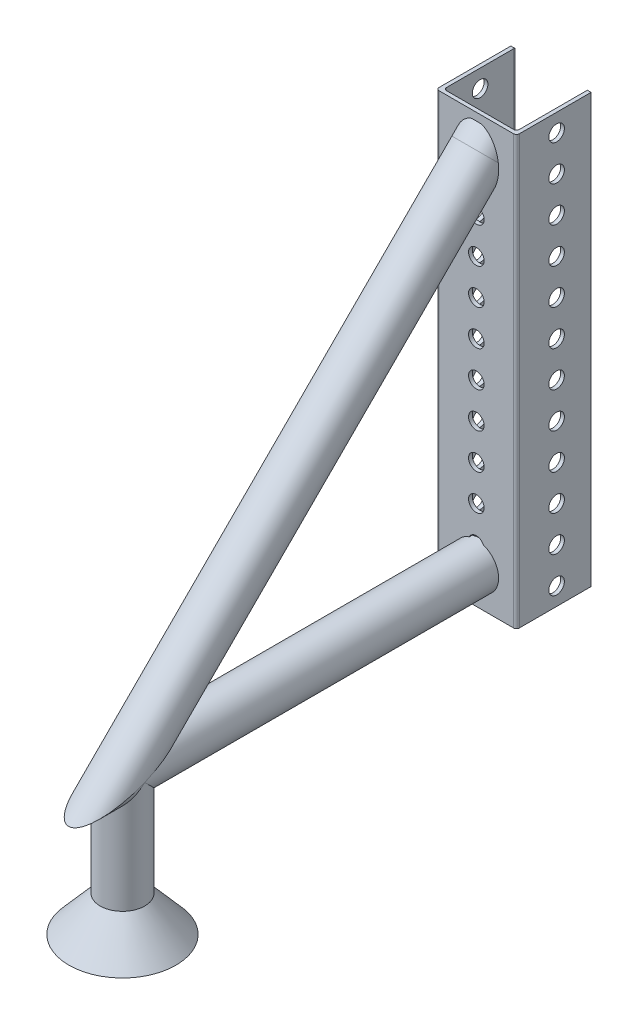
SolidWorks part; units mm, degrees
ref_plane "Front Plane" through (0, 0, 0) normal (0, 0, 1) x (1, 0, 0)
ref_plane "Top Plane" through (0, 0, 0) normal (0, 1, 0) x (1, 0, 0)
ref_plane "Right Plane" through (0, 0, 0) normal (1, 0, 0) x (0, 0, -1)
sketch "Sketch1" plane through (0, 0, 0) normal (0, 1, 0) x (1, 0, 0)
  line L1 (2, 0) -> (55.15, 0)
  line L2 (0, 2) -> (0, 55.15)
  line L3 (2, 57.15) -> (55.15, 57.15)
  line L4 (57.15, 2) -> (57.15, 55.15)
  line L5 (4.667, 54.483) -> (52.483, 54.483)
  line L6 (2.667, 52.483) -> (2.667, 4.667)
  line L7 (4.667, 2.667) -> (52.483, 2.667)
  line L8 (54.483, 52.483) -> (54.483, 4.667)
  arc A0 (55.15, 57.15) -> (57.15, 55.15) centre (55.15, 55.15) cw
  arc A1 (52.483, 54.483) -> (54.483, 52.483) centre (52.483, 52.483) cw
  arc A2 (55.15, 0) -> (57.15, 2) centre (55.15, 2) ccw
  arc A3 (52.483, 2.667) -> (54.483, 4.667) centre (52.483, 4.667) ccw
  arc A4 (2.667, 4.667) -> (4.667, 2.667) centre (4.667, 4.667) ccw
  arc A5 (2, 0) -> (0, 2) centre (2, 2) cw
  arc A6 (4.667, 54.483) -> (2.667, 52.483) centre (4.667, 52.483) ccw
  arc A7 (0, 55.15) -> (2, 57.15) centre (2, 55.15) cw
  point P15 (57.15, 0)
  point P22 (0, 0)
  point P27 (0, 57.15)
  dimension "D7" = 2
  dimension "D1" = 57.15
  dimension "D2" = 57.15
  dimension "D3" = 2.667
  dimension "D4" = 2.667
  dimension "D5" = 2.667
  dimension "D6" = 2.667
extrude "Boss-Extrude1" add sketch "Sketch1" along normal blind 304.8
sketch "Sketch2" plane through (0, 0, 0) normal (0, 0, 1) x (1, 0, 0)
  line L0 (28.575, 304.8) -> (28.575, 0) construction
  line L1 (2, 304.8) -> (55.15, 304.8) construction
  line L2 (2, 0) -> (55.15, 0) construction
  circle A0 centre (28.575, 292.1) radius 5.5563
  circle A1 centre (28.575, 266.7) radius 5.5563
  circle A2 centre (28.575, 241.3) radius 5.5562
  circle A3 centre (28.575, 215.9) radius 5.5562
  circle A4 centre (28.575, 190.5) radius 5.5562
  circle A5 centre (28.575, 165.1) radius 5.5563
  circle A6 centre (28.575, 139.7) radius 5.5563
  circle A7 centre (28.575, 114.3) radius 5.5562
  circle A8 centre (28.575, 88.9) radius 5.5562
  circle A9 centre (28.575, 63.5) radius 5.5562
  circle A10 centre (28.575, 38.1) radius 5.5563
  circle A11 centre (28.575, 12.7) radius 5.5562
  dimension "D1" = 11.1125
  dimension "D3" = 12.7
  dimension "D4" = 12.7
  dimension "D2" = 12
extrude "Cut-Extrude1" cut sketch "Sketch2" against normal blind 304.8
sketch "Sketch3" plane through (57.15, 0, -57.15) normal (-1, 0, 0) x (0, 0, 1)
  line L0 (28.575, 304.8) -> (28.575, 0) construction
  circle A0 centre (28.575, 292.1) radius 5.5563
  circle A1 centre (28.575, 266.7) radius 5.5563
  circle A2 centre (28.575, 241.3) radius 5.5562
  circle A3 centre (28.575, 215.9) radius 5.5562
  circle A4 centre (28.575, 190.5) radius 5.5562
  circle A5 centre (28.575, 165.1) radius 5.5563
  circle A6 centre (28.575, 139.7) radius 5.5563
  circle A7 centre (28.575, 114.3) radius 5.5562
  circle A8 centre (28.575, 88.9) radius 5.5562
  circle A9 centre (28.575, 63.5) radius 5.5562
  circle A10 centre (28.575, 38.1) radius 5.5563
  circle A11 centre (28.575, 12.7) radius 5.5562
  dimension "D1" = 11.1125
  dimension "D2" = 12
extrude "Cut-Extrude2" cut sketch "Sketch3" along normal blind 304.8
sketch "Sketch4" plane through (0, 0, -57.15) normal (0, 0, -1) x (-1, 0, 0)
  line L1 (-57.15, 304.8) -> (0, 304.8)
  line L2 (-57.15, 304.8) -> (-57.15, 0)
  line L3 (-57.15, 0) -> (0, 0)
  line L4 (0, 304.8) -> (0, 0)
extrude "Cut-Extrude3" cut sketch "Sketch4" against normal blind 4
ref_plane "Plane1" through (28.575, 0, 0) normal (1, 0, 0) x (0, 0, -1)
sketch "Sketch5" plane through (28.575, 0, 0) normal (1, 0, 0) x (0, 0, -1)
  line L0 (2, 279.4) -> (-252, 25.4)
  line L2 (2, 304.8) -> (2, 0) construction
  line L3 (-252, 25.4) -> (2, 25.4)
  line L4 (2, 0) -> (53.15, 0) construction
  line L5 (2, 279.4) -> (10.9803, 288.3803)
  dimension "D1" = 45
  dimension "D2" = 254
  dimension "D3" = 25.4
  dimension "D4" = 12.7
sweep "Sweep1" add path "Sketch5" circular profile diameter 31.75 parameters "D3"=31.75
sketch "Sketch18" plane through (0, 0, 0) normal (0, 1, 0) x (1, 0, 0)
  circle A0 centre (28.575, -252) radius 15.875
extrude "Boss-Extrude2" add sketch "Sketch18" along normal up to surface and the other way blind 25.4 up to face at (28.575, 9.525, 290.3256)
sketch "Sketch19" plane through (28.575, 0, 0) normal (1, 0, 0) x (0, 0, -1)
  line L0 (-252, -25.4) -> (-252, -76.2) construction
  line L1 (-267.875, -25.4) -> (-236.125, -25.4) construction
  line L2 (-236.125, -25.4) -> (-236.125, -50.8)
  line L3 (-236.125, -50.8) -> (-213.9, -76.2)
  line L4 (-213.9, -76.2) -> (-252, -76.2)
  line L5 (-236.125, -25.4) -> (-252, -25.4)
  line L6 (-252, -25.4) -> (-252, -76.2)
  dimension "D1" = 38.1
  dimension "D2" = 25.4
  dimension "D3" = 50.8
revolve "Revolve1" add sketch "Sketch19" angle 360 about L0
